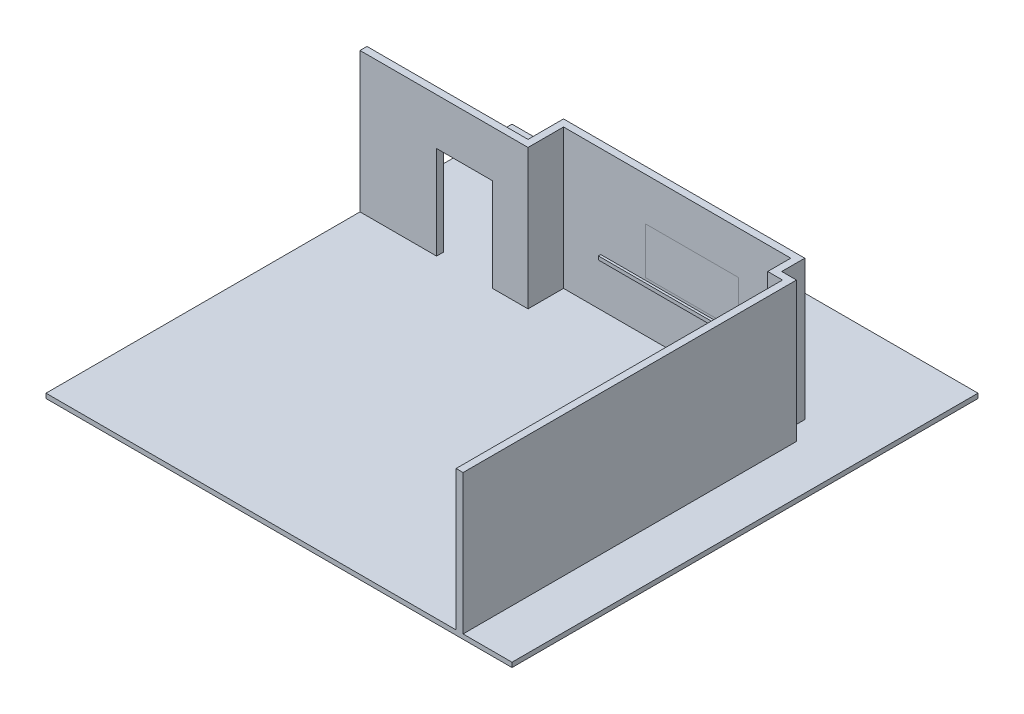
SolidWorks part; units mm, degrees
other "power_strip"
other "Cabinet"
other "window"
material "Concrete"
ref_plane "Front Plane" through (0, 0, 0) normal (0, 0, 1) x (1, 0, 0)
ref_plane "Top Plane" through (0, 0, 0) normal (0, 1, 0) x (1, 0, 0)
ref_plane "Right Plane" through (0, 0, 0) normal (1, 0, 0) x (0, 0, -1)
sketch "Sketch1" plane through (0, 0, 0) normal (0, 1, 0) x (1, 0, 0)
  line L1 (-5000, -5000) -> (5000, -5000)
  line L2 (-5000, -5000) -> (-5000, 5000)
  line L3 (-5000, 5000) -> (5000, 5000)
  line L4 (5000, -5000) -> (5000, 5000)
  line L5 (0, 5000) -> (0, -5000) construction
  line L6 (-5000, 0) -> (5000, 0) construction
  point P0 (0, 0)
  dimension "D1" = 10000
  dimension "D2" = 10000
extrude "Boss-Extrude1" add sketch "Sketch1" against normal blind 100
sketch "Sketch3" plane through (0, 0, 0) normal (0, 1, 0) x (1, 0, 0)
  line L0 (3482.5, 2500) -> (-1394.3, 2500)
  line L1 (-1394.3, 2500) -> (-1394.3, 1738)
  line L2 (-1394.3, 1738) -> (-5000, 1738)
  line L3 (-5000, 5000) -> (-5000, -5000) construction
  line L4 (3482.5, 2500) -> (3482.5, 2005)
  line L5 (3482.5, 2005) -> (3800, 2005)
  line L6 (3800, 2005) -> (3800, -5000)
  line L7 (-5000, -5000) -> (5000, -5000) construction
  line L8 (3950, 2155) -> (3950, -5000)
  line L9 (3632.5, 2155) -> (3950, 2155)
  line L10 (3632.5, 2650) -> (3632.5, 2155)
  line L11 (3632.5, 2650) -> (-1544.3, 2650)
  line L12 (-1544.3, 2650) -> (-1544.3, 1888)
  line L13 (-1544.3, 1888) -> (-5000, 1888)
  line L14 (5000, -5000) -> (5000, 5000) construction
  line L15 (5000, 5000) -> (-5000, 5000) construction
  line L16 (-5000, 1888) -> (-5000, 1738)
  line L17 (3800, -5000) -> (3950, -5000)
  point P23 (-5000, 2038.253)
  dimension "D2" = 1200
  dimension "D3" = 2500
  dimension "D4" = 495
  dimension "D5" = 317.5
  dimension "D6" = 762
  dimension "D7" = 4876.8
  dimension "D1" = 150
extrude "Boss-Extrude2" add sketch "Sketch3" along normal blind 3000
sketch "Sketch4" plane through (0, 0, -2500) normal (0, 0, 1) x (1, 0, 0)
  line L0 (-1394.3, 0) -> (3482.5, 0) construction
  line L1 (364.9, 1079.5) -> (2364.9, 1079.5)
  line L2 (364.9, 1079.5) -> (364.9, 2079.5)
  line L3 (364.9, 2079.5) -> (2364.9, 2079.5)
  line L4 (2364.9, 1079.5) -> (2364.9, 2079.5)
  line L5 (3482.5, 3000) -> (3482.5, 0) construction
  line L6 (-5000, 0) -> (3800, 0) construction
  line L7 (-3356.3, 0) -> (-2156.3, 0)
  line L8 (-3356.3, 0) -> (-3356.3, 2000)
  line L9 (-3356.3, 2000) -> (-2156.3, 2000)
  line L10 (-2156.3, 0) -> (-2156.3, 2000)
  line L11 (-1394.3, 3000) -> (-1394.3, 0) construction
  point P14 (-2495.3464, 2921.6501)
  dimension "D1" = 1079.5
  dimension "D2" = 1117.6
  dimension "D3" = 2000
  dimension "D4" = 1000
  dimension "D5" = 762
  dimension "D6" = 1200
  dimension "D7" = 2000
sketch "Sketch5" plane through (0, 0, 0) normal (0, 1, 0) x (1, 0, 0)
  line L0 (3800, 2005) -> (3800, -5000) construction
  line L1 (3800, 887.4) -> (3241.2, 887.4)
  line L2 (3800, 887.4) -> (3800, -37.16)
  line L3 (3800, -37.16) -> (3241.2, -37.16)
  line L4 (3241.2, 887.4) -> (3241.2, -37.16)
  line L5 (3482.5, 2005) -> (3800, 2005) construction
  dimension "D1" = 558.8
  dimension "D2" = 924.56
  dimension "D3" = 1117.6
extrude "Cut-Extrude1" cut sketch "Sketch4" against normal through all both and the other way through all
extrude "Boss-Extrude3" add sketch "Sketch4<2>" against normal up to surface (150 mm away) from surface separate body contours L1 L4 L3 L2 region at (1364.9, 1579.5, -2500) up to face at (1364.9, 1579.5, -2650) starting at face at (1364.9, 1579.5, -2500)
sketch "Sketch4<2>" plane through (0, 0, -2500) normal (0, 0, 1) x (1, 0, 0) same geometry as "Sketch4"
extrude "Boss-Extrude4" add sketch "Sketch5" along normal blind 1900 separate body
sketch "Sketch6" plane through (0, 0, -2500) normal (0, 0, 1) x (1, 0, 0)
  line L1 (-594.3, 1028.7) -> (3482.5, 1028.7)
  line L2 (-594.3, 1028.7) -> (-594.3, 952.5)
  line L3 (-594.3, 952.5) -> (3482.5, 952.5)
  line L4 (3482.5, 1028.7) -> (3482.5, 952.5)
  line L5 (3482.5, 3000) -> (3482.5, 0) construction
  line L6 (2364.9, 1079.5) -> (364.9, 1079.5) construction
  line L7 (-1394.3, 3000) -> (-1394.3, 0) construction
  dimension "D1" = 76.2
  dimension "D2" = 50.8
  dimension "D3" = 800
extrude "Boss-Extrude5" add sketch "Sketch6" along normal blind 50.8 separate body
